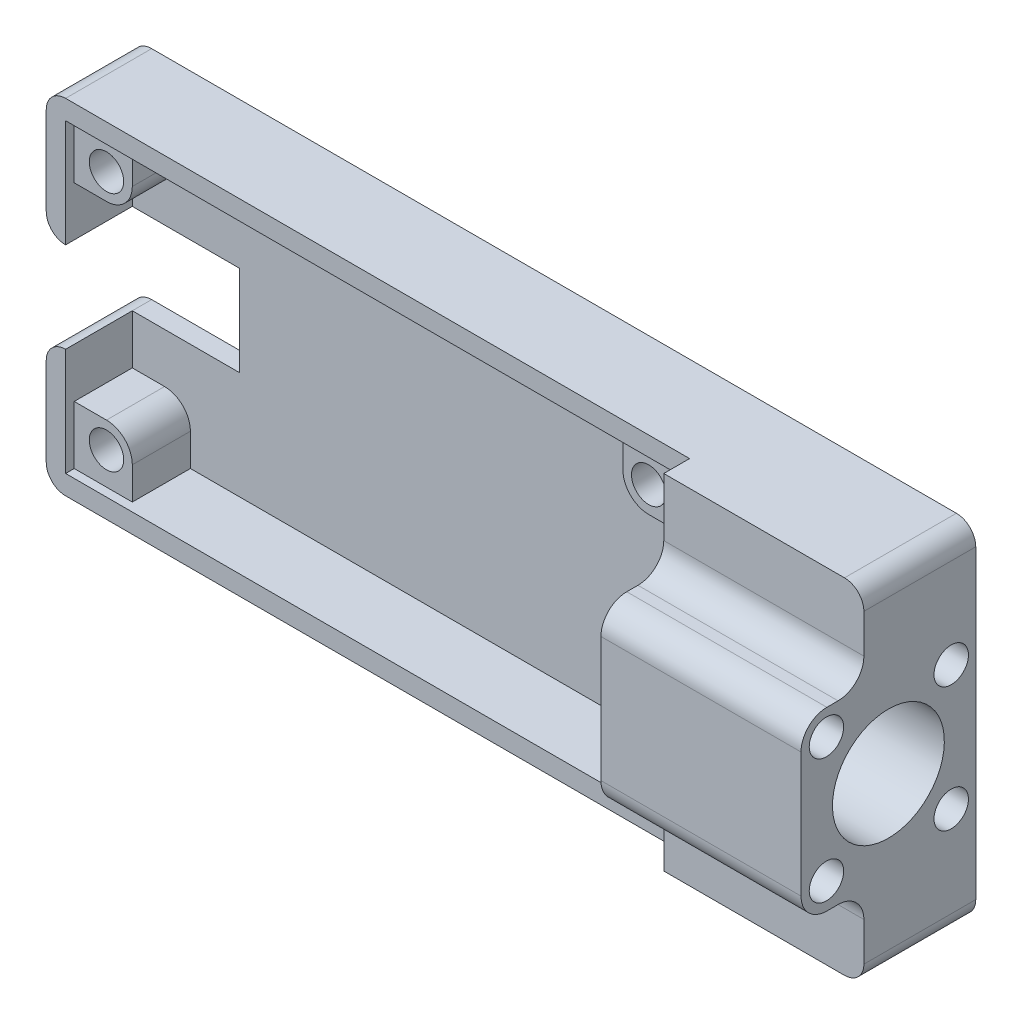
SolidWorks part; units mm, degrees
ref_plane "Front Plane" through (0, 0, 0) normal (0, 0, 1) x (1, 0, 0)
ref_plane "Top Plane" through (0, 0, 0) normal (0, 1, 0) x (1, 0, 0)
ref_plane "Right Plane" through (0, 0, 0) normal (1, 0, 0) x (0, 0, -1)
sketch "Sketch4" plane through (0, 0, 0) normal (0, 0, 1) x (1, 0, 0)
  line L0 (0, 40) -> (0, 25.25)
  line L1 (0, 0) -> (98, 0)
  line L2 (0, 14.75) -> (0, 0)
  line L3 (0, 40) -> (98, 40)
  line L4 (98, 0) -> (98, 40)
  line L5 (14.7, 14.75) -> (14.7, 25.25)
  line L6 (14.7, 25.25) -> (0, 25.25)
  line L7 (14.7, 14.75) -> (0, 14.75)
  line L8 (14.7, 20) -> (98, 20) construction
  line L9 (0, 0) -> (0, 40) construction
  dimension "D1" = 40
  dimension "D2" = 14.7
  dimension "D4" = 10.5
  dimension "D5" = 98
extrude "body" add sketch "Sketch4" along normal blind 10
sketch "Sketch10" plane through (0, 0, 10) normal (0, 0, 1) x (1, 0, 0)
  line L0 (0, 40) -> (0, 0) construction
  line L1 (0, 20) -> (98, 20) construction
  line L2 (98, 0) -> (98, 40) construction
  line L4 (72.75, 2.25) -> (2.25, 2.25)
  line L5 (72.75, 2.25) -> (72.75, 37.75)
  line L6 (72.75, 37.75) -> (2.25, 37.75)
  line L7 (2.25, 2.25) -> (2.25, 37.75)
  line L8 (72.75, 2.25) -> (2.25, 37.75) construction
  line L9 (72.75, 37.75) -> (2.25, 2.25) construction
  point P8 (37.5, 20)
  dimension "D1" = 70.5
  dimension "D2" = 35.5
  dimension "D3" = 2.25
extrude "pcb-recess" cut sketch "Sketch10" against normal offset from surface (7.75 mm away) 2.25 up to face at (28.175, 20, 0)
sketch "Sketch11" plane through (0, 0, 2.25) normal (0, 0, 1) x (1, 0, 0)
  line L0 (2.25, 37.75) -> (2.25, 2.25) construction
  line L1 (2.25, 20) -> (72.75, 20) construction
  line L2 (72.75, 2.25) -> (72.75, 37.75) construction
  line L3 (6, 37.75) -> (6, 2.25) construction
  line L4 (72.75, 37.75) -> (2.25, 37.75) construction
  line L5 (2.25, 2.25) -> (72.75, 2.25) construction
  line L6 (69, 37.75) -> (69, 2.25) construction
  line L7 (72.75, 37.75) -> (2.25, 37.75) construction
  line L8 (2.25, 2.25) -> (72.75, 2.25) construction
  line L9 (2.25, 34) -> (72.75, 34) construction
  line L10 (2.25, 6) -> (72.75, 6) construction
  line L11 (6, 31) -> (2.25, 31)
  line L12 (9, 34) -> (9, 37.75)
  line L13 (2.25, 37.75) -> (72.75, 37.75) construction
  line L14 (9, 37.75) -> (2.25, 37.75)
  line L15 (2.25, 37.75) -> (2.25, 31)
  line L16 (66, 34) -> (66, 37.75)
  line L17 (66, 37.75) -> (72.75, 37.75)
  line L18 (72.75, 37.75) -> (72.75, 31)
  line L19 (72.75, 31) -> (69, 31)
  line L20 (69, 9) -> (72.75, 9)
  line L21 (72.75, 9) -> (72.75, 2.25)
  line L22 (72.75, 2.25) -> (66, 2.25)
  line L23 (72.75, 2.25) -> (2.25, 2.25) construction
  line L24 (66, 2.25) -> (66, 6)
  line L25 (2.25, 9) -> (6, 9)
  line L26 (2.25, 9) -> (2.25, 2.25)
  line L27 (2.25, 2.25) -> (9, 2.25)
  line L28 (9, 2.25) -> (9, 6)
  circle A0 centre (6, 34) radius 3
  circle A1 centre (69, 34) radius 3
  circle A2 centre (69, 6) radius 3
  circle A3 centre (6, 6) radius 3
  point P20 (37.5, 20)
  line M9 (2.25, 14.75) -> (2.25, 2.25)
  line M10 (2.25, 2.25) -> (72.75, 2.25)
  line M11 (72.75, 2.25) -> (72.75, 37.75)
  line M12 (72.75, 37.75) -> (2.25, 37.75)
  line M13 (2.25, 37.75) -> (2.25, 25.25)
  dimension "D5" = 6
  dimension "D6" = 6
  dimension "D7" = 6
  dimension "D8" = 6
  dimension "D1" = 31.5
  dimension "D2" = 31.5
  dimension "D3" = 14
  dimension "D4" = 14
extrude "pcb-boss" add sketch "Sketch11" along normal offset from surface (6.75 mm away) 1 contours A0 | A0 L12 L11 M12 M13 | A3 L25 L28 M9 M10 | A3 | A2 | A2 L24 L20 M10 M11 | A1 L19 L16 M11 M12 | A1 region at (5.625, 2.3455, 2.25) region at (72.6545, 5.625, 2.25) region at (69.375, 37.6545, 2.25) region at (4.125, 31.0955, 2.25) region at (6, 34, 2.25) region at (69, 34, 2.25) region at (69, 6, 2.25) region at (6, 6, 2.25) up to face at (29.2083, 20, 10)
fillet "Fillet2" radius 2.25 2 edges at (0, 14.75, 5) (0, 25.25, 5)
sketch "Sketch23" plane through (98, 0, 0) normal (1, 0, 0) x (0, 0, -1)
  line L0 (-10, 0) -> (-10, 40) construction
  line L1 (-10, 30.25) -> (-20.3, 30.25)
  line L2 (-10, 30.25) -> (-10, 9.75)
  line L3 (-10, 9.75) -> (-20.3, 9.75)
  line L4 (-20.3, 30.25) -> (-20.3, 9.75)
  line L5 (-10, 20) -> (-20.3, 20) construction
  dimension "D1" = 20.5
  dimension "D2" = 10.3
extrude "Boss-Extrude2" add sketch "Sketch23" against normal offset from surface (23.25 mm away) 2 up to face at (72.75, 20, 7.5625)
sketch "Sketch24" plane through (0, 0, 10) normal (0, 0, 1) x (1, 0, 0)
  line L1 (74.75, 30.25) -> (98, 30.25)
  line L2 (74.75, 30.25) -> (74.75, 40)
  line L3 (74.75, 40) -> (98, 40)
  line L4 (98, 30.25) -> (98, 40)
  line L5 (74.75, 9.75) -> (98, 9.75)
  line L6 (74.75, 9.75) -> (74.75, 0)
  line L7 (74.75, 0) -> (98, 0)
  line L8 (98, 9.75) -> (98, 0)
extrude "Boss-Extrude3" add sketch "Sketch24" along normal blind 3
sketch "Sketch25" plane through (98, 0, 0) normal (1, 0, 0) x (0, 0, -1)
  line L0 (-20.3, 20) -> (0, 20) construction
  line L1 (-20.3, 30.25) -> (-20.3, 9.75) construction
  line L2 (0, 0) -> (0, 40) construction
  circle A0 centre (-10.15, 20) radius 6.5
  dimension "D1" = 13
extrude "Cut-Extrude9" cut sketch "Sketch25" against normal blind 15
sketch "Sketch26" plane through (83, 0, 0) normal (1, 0, 0) x (0, 0, -1)
  line L0 (-10.15, 26.5) -> (-10.15, 13.5)
  circle A0 centre (-10.15, 20) radius 6.5 construction
  circle A1 centre (-10.15, 20) radius 6.5 construction
  arc A2 (-10.15, 26.5) -> (-10.15, 13.5) centre (-10.15, 20) cw
extrude "Cut-Extrude10" cut sketch "Sketch26" against normal up to surface (10.25 mm away) up to face at (72.75, 20, 7.5625)
fillet "Fillet7" radius 3 4 edges at (86.375, 9.75, 13) (86.375, 9.75, 20.3) (86.375, 30.25, 20.3) (86.375, 30.25, 13)
fillet "Fillet8" radius 2.25 4 edges at (98, 40, 6.5) (98, 0, 6.5) (0, 0, 5) (0, 40, 5)
sketch "Sketch27" plane through (98, 0, 0) normal (1, 0, 0) x (0, 0, -1)
  line L0 (-25.5029, 27.3) -> (7.3002, 27.3) construction
  line L1 (-25.5029, 12.8) -> (7.3002, 12.8) construction
  line L2 (-17.35, 33.6548) -> (-17.35, 4.2852) construction
  line L3 (-2.85, 33.6548) -> (-2.85, 4.2852) construction
  line L4 (-10.15, 26.5) -> (-10.15, 13.5) construction
  circle A1 centre (-17.35, 27.3) radius 2
  circle A2 centre (-2.85, 27.3) radius 2
  circle A3 centre (-2.85, 12.8) radius 2
  circle A4 centre (-17.35, 12.8) radius 2
  point P10 (-10.15, 20)
  point P19 (-17.65, 27.5)
  point P20 (-2.65, 27.5)
  point P21 (-2.65, 27.5)
  point P22 (0, 0)
  point P23 (-17.65, 27.5)
  point P24 (-17.65, 27.5)
  dimension "D5" = 4
  dimension "D6" = 4
  dimension "D7" = 4
  dimension "D8" = 4
  dimension "D1" = 7.3
  dimension "D2" = 14.5
  dimension "D3" = 7.3
  dimension "D4" = 14.5
extrude "Cut-Extrude11" cut sketch "Sketch27" against normal blind 5.5
sketch "Sketch12" plane through (0, 0, 9) normal (0, 0, 1) x (1, 0, 0)
  circle A0 centre (6, 34) radius 2
  circle A1 centre (69, 34) radius 2
  circle A2 centre (69, 6) radius 2
  circle A3 centre (6, 6) radius 2
  dimension "D1" = 4
  dimension "D2" = 4
  dimension "D3" = 4
  dimension "D4" = 4
extrude "Cut-Extrude5" cut sketch "Sketch12" against normal blind 4.5
